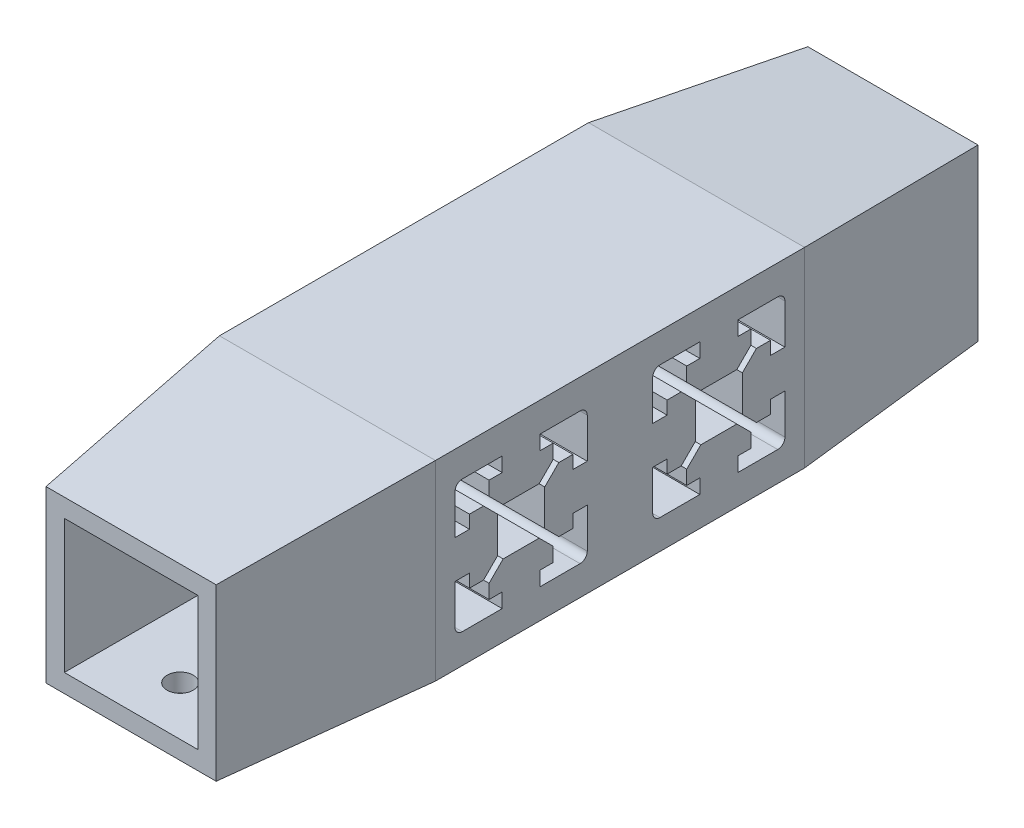
SolidWorks part; units mm, degrees
ref_plane "Front Plane" through (0, 0, 0) normal (0, 0, 1) x (1, 0, 0)
ref_plane "Top Plane" through (0, 0, 0) normal (0, 1, 0) x (1, 0, 0)
ref_plane "Right Plane" through (0, 0, 0) normal (1, 0, 0) x (0, 0, -1)
sketch "Sketch3" plane through (0, 0, 0) normal (1, 0, 0) x (0, 0, -1)
  line L0 (-10.1, 2.9) -> (-10.1, 9)
  line L5 (0, 0) -> (33.3867, 33.3867) construction
  line L6 (2.9, 10.1) -> (9, 10.1)
  line L7 (0, -29.658) -> (0, 39.9767) construction
  line L8 (2.9, 10.1) -> (2.9, 7.9)
  line L9 (2.9, 7.9) -> (4.9, 7.9)
  line L10 (4.9, 7.9) -> (4.9, 5.749)
  line L11 (4.9, 5.749) -> (2.7515, 3.6005)
  line L12 (2.7515, 3.6005) -> (-2.7515, 3.6005)
  line L13 (3.6005, 2.7515) -> (3.6005, -2.7515)
  line L14 (5.749, 4.9) -> (3.6005, 2.7515)
  line L15 (7.9, 4.9) -> (5.749, 4.9)
  line L16 (7.9, 2.9) -> (7.9, 4.9)
  line L17 (10.1, 2.9) -> (7.9, 2.9)
  line L18 (10.1, 2.9) -> (10.1, 9)
  line L19 (-10.1, 2.9) -> (-7.9, 2.9)
  line L20 (-7.9, 2.9) -> (-7.9, 4.9)
  line L21 (-7.9, 4.9) -> (-5.749, 4.9)
  line L22 (-5.749, 4.9) -> (-3.6005, 2.7515)
  line L23 (-3.6005, 2.7515) -> (-3.6005, -2.7515)
  line L24 (-4.9, 5.749) -> (-2.7515, 3.6005)
  line L25 (-4.9, 7.9) -> (-4.9, 5.749)
  line L26 (-2.9, 7.9) -> (-4.9, 7.9)
  line L27 (-2.9, 10.1) -> (-2.9, 7.9)
  line L28 (-2.9, 10.1) -> (-9, 10.1)
  line L29 (-37.4596, 0) -> (35.8917, 0) construction
  line L30 (-2.9, -10.1) -> (-9, -10.1)
  line L31 (-2.9, -10.1) -> (-2.9, -7.9)
  line L32 (-2.9, -7.9) -> (-4.9, -7.9)
  line L33 (-4.9, -7.9) -> (-4.9, -5.749)
  line L34 (-4.9, -5.749) -> (-2.7515, -3.6005)
  line L35 (-5.749, -4.9) -> (-3.6005, -2.7515)
  line L36 (-7.9, -4.9) -> (-5.749, -4.9)
  line L37 (-7.9, -2.9) -> (-7.9, -4.9)
  line L38 (-10.1, -2.9) -> (-7.9, -2.9)
  line L39 (10.1, -2.9) -> (10.1, -9)
  line L40 (10.1, -2.9) -> (7.9, -2.9)
  line L41 (7.9, -2.9) -> (7.9, -4.9)
  line L42 (7.9, -4.9) -> (5.749, -4.9)
  line L43 (5.749, -4.9) -> (3.6005, -2.7515)
  line L44 (2.7515, -3.6005) -> (-2.7515, -3.6005)
  line L45 (4.9, -5.749) -> (2.7515, -3.6005)
  line L46 (4.9, -7.9) -> (4.9, -5.749)
  line L47 (2.9, -7.9) -> (4.9, -7.9)
  line L48 (2.9, -10.1) -> (2.9, -7.9)
  line L49 (2.9, -10.1) -> (9, -10.1)
  line L50 (-10.1, -2.9) -> (-10.1, -9)
  line L52 (-15.1, 14.6) -> (13.1, 14.6)
  line L53 (-15.1, 14.6) -> (-15.1, -14.6)
  line L54 (-15.1, -14.6) -> (13.1, -14.6)
  line L55 (13.1, 14.6) -> (13.1, -14.6)
  arc A0 (9, 10.1) -> (10.1, 9) centre (9, 9) cw
  arc A3 (-9, 10.1) -> (-10.1, 9) centre (-9, 9) ccw
  arc A4 (-9, -10.1) -> (-10.1, -9) centre (-9, -9) cw
  arc A7 (9, -10.1) -> (10.1, -9) centre (9, -9) ccw
  point P0 (0, 0)
  dimension "D3" = 1.1
  dimension "D1" = 45
  dimension "D2" = 20.2
  dimension "D4" = 6.1
  dimension "D5" = 2.2
  dimension "D6" = 2
  dimension "D7" = 2.151
  dimension "D8" = 5.503
  dimension "D9" = 4.5
  dimension "D10" = 4.5
  dimension "D11" = 5
  dimension "D12" = 3
extrude "Boss-Extrude1" add sketch "Sketch3" along normal blind 3 contours L49 A7 L39 L40 L41 L42 L43 L13 L14 L15 L16 L17 L18 A0 L6 L8 L9 L10 L11 L12 L24 L25 L26 L27 L28 A3 L0 L19 L20 L21 L22 L23 L35 L36 L37 L38 L50 A4 L30 L31 L32 L33 L34 L44 L45 L46 L47 L48 | L55 L52 L53 L54 A7 L49 L48 L47 L46 L45 L44 L34 L33 L32 L31 L30 A4 L50 L38 L37 L36 L35 L23 L22 L21 L20 L19 L0 A3 L28 L27 L26 L25 L24 L12 L11 L10 L9 L8 L6 A0 L18 L17 L16 L15 L14 L13 L43 L42 L41 region at (0, 0, 0) region at (0, 14.1941, 1)
extrude "Boss-Extrude2" add sketch "Sketch3<3>" along normal blind 30 from surface starting at face at (3, 0, 1)
sketch "Sketch3<3>" plane through (0, 0, 0) normal (1, 0, 0) x (0, 0, -1) same geometry as "Sketch3"
ref_plane "Plane1" through (0, 0, -43.1) normal (0, 0, -1) x (-1, 0, 0)
sketch "Sketch6" plane through (0, 0, -43.1) normal (0, 0, -1) x (-1, 0, 0)
  line L1 (-29.5, -14.6) -> (-3.5, -14.6)
  line L2 (-29.5, -14.6) -> (-29.5, 11.4)
  line L3 (-29.5, 11.4) -> (-3.5, 11.4)
  line L4 (-3.5, -14.6) -> (-3.5, 11.4)
  line L5 (-16.5, -22.5801) -> (-16.5, 24.7352) construction
  line L6 (-26.7, 8.6) -> (-6.3, 8.6)
  line L7 (-26.7, 8.6) -> (-26.7, -11.8)
  line L8 (-26.7, -11.8) -> (-6.3, -11.8)
  line L9 (-6.3, 8.6) -> (-6.3, -11.8)
  line L10 (-33, -14.6) -> (0, -14.6) construction
  point P4 (-16.5, -14.6)
  point P5 (-16.5, -14.6)
  dimension "D1" = 20.4
  dimension "D2" = 20.4
  dimension "D3" = 2.8
  dimension "D4" = 2.8
  dimension "D5" = 2.8
  dimension "D6" = 2.8
loft "Loft2" add section face at (16.5, 0, -13.1) section "Sketch6"
extrude "Cut-Extrude2" cut sketch "Sketch6<4>" against normal blind 30 contours L8 L5 L6 L7 | L5 L8 L9 L6 region at (21.6, -1.6, -43.1) region at (11.4, -1.6, -43.1)
sketch "Sketch6<4>" plane through (0, 0, -43.1) normal (0, 0, -1) x (-1, 0, 0) same geometry as "Sketch6"
sketch "Sketch8" plane through (0, -11.8, 0) normal (0, 1, 0) x (1, 0, 0)
  line L0 (16.5, 43.1) -> (16.5, 13.1) construction
  line L1 (29.5, 43.1) -> (3.5, 43.1) construction
  line L2 (33, 13.1) -> (0, 13.1) construction
  circle A0 centre (16.5, 35.6) radius 2
  circle A1 centre (16.5, 20.6) radius 2
  dimension "D3" = 4
  dimension "D1" = 7.5
  dimension "D2" = 15
extrude "Cut-Extrude3" cut sketch "Sketch8" against normal blind 30
mirror "Mirror2" about plane through (3, 0, 15.1) normal (0, 0, -1) of bodies 106
